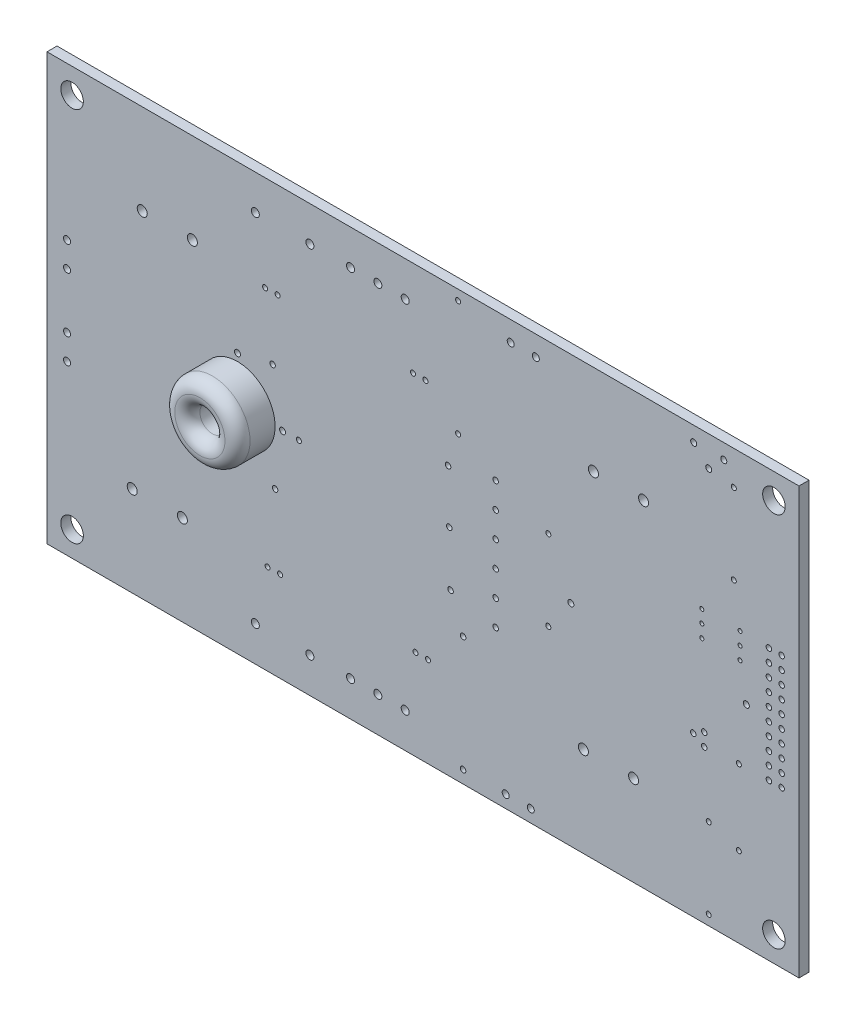
SolidWorks part; units mm, degrees
ref_plane "Спереди" through (0, 0, 0) normal (0, 0, 1) x (1, 0, 0)
ref_plane "Сверху" through (0, 0, 0) normal (0, 1, 0) x (1, 0, 0)
ref_plane "Справа" through (0, 0, 0) normal (1, 0, 0) x (0, 0, -1)
sketch "Эскиз1" plane through (0, 0, 0) normal (0, 0, 1) x (1, 0, 0)
  line L0 (-22.6071, 0) -> (23.7373, 0) construction
  line L1 (-75, -42.5) -> (75, -42.5)
  line L2 (-75, -42.5) -> (-75, 42.5)
  line L3 (-75, 42.5) -> (75, 42.5)
  line L4 (75, -42.5) -> (75, 42.5)
  line L5 (0, 0) -> (0, 31.6453) construction
  circle A0 centre (-70, -37.5) radius 2.25
  circle A1 centre (70, -37.5) radius 2.25
  circle A2 centre (70, 37.5) radius 2.25
  circle A3 centre (-70, 37.5) radius 2.25
  dimension "D3" = 4.5
  dimension "D1" = 150
  dimension "D2" = 85
  dimension "D4" = 5
  dimension "D5" = 5
extrude "Вытянуть1" add sketch "Эскиз1" along normal blind 2
sketch "Эскиз2" plane through (0, 0, 2) normal (0, 0, 1) x (1, 0, 0)
  line L0 (-75, 42.5) -> (-75, -42.5) construction
  line L1 (-75, -42.5) -> (75, -42.5) construction
  line L2 (-33.45, 35.5) -> (-22.55, 35.5) construction
  line L3 (-14.45, -35.5) -> (-3.55, -35.5) construction
  line L4 (69, 11.5) -> (71.54, 11.5) construction
  line L5 (14.5, -12.2) -> (47.2663, -12.2) construction
  line L6 (14.5, -12.2) -> (26.9466, 0.2466) construction
  line L7 (-24.75, 0.5) -> (5.25, 0.5) construction
  line L14 (63, -26.5) -> (63, -11.5) construction
  line L15 (-14.45, 35.5) -> (-3.55, 35.5) construction
  line L16 (-33.45, -35.5) -> (-22.55, -35.5) construction
  line L18 (14.5, -22.58) -> (14.5, -12.2) construction
  circle A0 centre (69, 11.5) radius 0.55
  circle A1 centre (71.54, 11.5) radius 0.55
  circle A2 centre (69, 8.96) radius 0.55
  circle A3 centre (71.54, 8.96) radius 0.55
  circle A4 centre (69, 6.42) radius 0.55
  circle A5 centre (71.54, 6.42) radius 0.55
  circle A6 centre (69, 3.88) radius 0.55
  circle A7 centre (71.54, 3.88) radius 0.55
  circle A8 centre (69, 1.34) radius 0.55
  circle A9 centre (71.54, 1.34) radius 0.55
  circle A10 centre (69, -1.2) radius 0.55
  circle A11 centre (71.54, -1.2) radius 0.55
  circle A12 centre (69, -3.74) radius 0.55
  circle A13 centre (71.54, -3.74) radius 0.55
  circle A14 centre (69, -6.28) radius 0.55
  circle A15 centre (71.54, -6.28) radius 0.55
  circle A16 centre (69, -8.82) radius 0.55
  circle A17 centre (71.54, -8.82) radius 0.55
  circle A18 centre (69, -11.36) radius 0.55
  circle A19 centre (71.54, -11.36) radius 0.55
  circle A20 centre (63, -26.5) radius 0.5
  circle A21 centre (63, -11.5) radius 0.5
  circle A22 centre (-14.45, 35.5) radius 0.8
  circle A23 centre (-9, 35.5) radius 0.8
  circle A24 centre (-3.55, 35.5) radius 0.8
  circle A25 centre (-33.45, 35.5) radius 0.8
  circle A26 centre (-24.75, 0.5) radius 0.5
  circle A27 centre (-22.55, 35.5) radius 0.8
  circle A28 centre (-33.45, -35.5) radius 0.8
  circle A29 centre (5.25, 0.5) radius 0.55
  circle A30 centre (-22.55, -35.5) radius 0.8
  circle A31 centre (-14.45, -35.5) radius 0.8
  circle A32 centre (-9, -35.5) radius 0.8
  circle A33 centre (-3.55, -35.5) radius 0.8
  circle A37 centre (14.5, 13.2) radius 0.55
  circle A38 centre (14.5, 8.12) radius 0.55
  circle A39 centre (14.5, -2.04) radius 0.55
  circle A40 centre (14.5, 3.04) radius 0.55
  circle A41 centre (14.5, -7.12) radius 0.55
  circle A45 centre (14.5, -12.2) radius 0.55
  dimension "D3" = 1.1
  dimension "D4" = 2.54
  dimension "D7" = 1
  dimension "D8" = 138
  dimension "D9" = 60.55
  dimension "D10" = 10.9
  dimension "D11" = 1.1
  dimension "D12" = 78
  dimension "D13" = 1.6
  dimension "D19" = 1.6
  dimension "D20" = 5.45
  dimension "D23" = 30
  dimension "D14" = 10.9
  dimension "D26" = 10.9
  dimension "D27" = 1.1
  dimension "D28" = 43
  dimension "D29" = 50.25
  dimension "D30" = 5.08
  dimension "D32" = 30.3
  dimension "D6" = 15
  dimension "D33" = 5.08
  dimension "D34" = 5.08
  dimension "D36" = 5.08
  dimension "D42" = 1.6
  dimension "D24" = 54
  dimension "D35" = 5.08
  dimension "D1" = 144
  dimension "D5" = 16
  dimension "D15" = 41.55
  dimension "D16" = 78
  dimension "D17" = 7
  dimension "D18" = 7
  dimension "D21" = 41.55
  dimension "D22" = 60.55
  dimension "D25" = 45
  dimension "D31" = 89.5
extrude "Вырез-Вытянуть1" cut sketch "Эскиз2" against normal blind 2
sketch "Эскиз3" plane through (0, 0, 2) normal (0, 0, 1) x (1, 0, 0)
  line L0 (-75, -42.5) -> (75, -42.5) construction
  line L1 (-75, 42.5) -> (-75, -42.5) construction
  line L2 (-56, 24.5) -> (-46, 24.5) construction
  line L3 (56.095, -10.75) -> (51.9719, -10.75) construction
  line L4 (56.095, -9.48) -> (56.095, -32.4484) construction
  line L5 (55, -12.02) -> (55, -7.4533) construction
  line L6 (16.5, -40) -> (21.5, -40) construction
  line L7 (-71, 7) -> (-71, 12) construction
  line L8 (-71, -9) -> (-71, -4) construction
  line L9 (-75, -42.5) -> (75, -42.5) construction
  line L11 (25, -6.75) -> (25, 9.25) construction
  line L12 (57, -40.5) -> (57, -24.5) construction
  line L14 (47.25, 45) -> (47.25, 55) construction
  line L16 (34, 24.5) -> (44, 24.5) construction
  line L17 (32, -24.5) -> (42, -24.5) construction
  line L18 (-58, -24.5) -> (-48, -24.5) construction
  line L19 (62, 19.75) -> (62, 35.75) construction
  line L20 (63.24, 11.58) -> (63.24, 6.5) construction
  line L21 (55.62, 6.5) -> (55.62, 12.7862) construction
  line L22 (55.62, 6.5) -> (63.24, 6.5) construction
  line L23 (54, 39.5) -> (60, 39.5) construction
  line L24 (17.5, 38.5) -> (22.5, 38.5) construction
  line L25 (29.5, -0.5) -> (64.5, -0.5) construction
  circle A0 centre (-56, 24.5) radius 1
  circle A1 centre (-46, 24.5) radius 1
  circle A2 centre (-58, -24.5) radius 1
  circle A3 centre (-48, -24.5) radius 1
  circle A4 centre (54, 39.5) radius 0.6
  circle A5 centre (60, 39.5) radius 0.6
  circle A6 centre (56.095, -9.48) radius 0.55
  circle A7 centre (56.095, -12.02) radius 0.55
  circle A8 centre (53.905, -10.75) radius 0.55
  circle A9 centre (70, -37.5) radius 2.25 construction
  circle A10 centre (16.5, -40) radius 0.7
  circle A12 centre (21.5, -40) radius 0.7
  circle A13 centre (-71, 7) radius 0.7
  circle A14 centre (-71, 12) radius 0.7
  circle A15 centre (-71, -9) radius 0.7
  circle A16 centre (-71, -4) radius 0.7
  circle A17 centre (25, -6.75) radius 0.5
  circle A18 centre (25, 9.25) radius 0.5
  circle A20 centre (57, -40.5) radius 0.5
  circle A21 centre (57, -24.5) radius 0.5
  circle A28 centre (34, 24.5) radius 1
  circle A29 centre (44, 24.5) radius 1
  circle A30 centre (32, -24.5) radius 1
  circle A31 centre (42, -24.5) radius 1
  circle A34 centre (57, 36.5) radius 0.6
  circle A35 centre (17.5, 38.5) radius 0.7
  circle A36 centre (62, 19.75) radius 0.5
  circle A37 centre (62, 35.75) radius 0.5
  circle A38 centre (63.24, 11.58) radius 0.4
  circle A39 centre (63.24, 6.5) radius 0.4
  circle A40 centre (55.62, 9.04) radius 0.4
  circle A41 centre (63.24, 9.04) radius 0.4
  circle A42 centre (55.62, 6.5) radius 0.4
  circle A43 centre (55.62, 11.58) radius 0.4
  circle A44 centre (22.5, 38.5) radius 0.7
  circle A45 centre (64.5, -0.5) radius 0.6
  circle A46 centre (29.5, -0.5) radius 0.6
  dimension "D5" = 1.1
  dimension "D8" = 2.54
  dimension "D9" = 2.19
  dimension "D10" = 1.095
  dimension "D11" = 15
  dimension "D16" = 91.5
  dimension "D17" = 5
  dimension "D18" = 49.5
  dimension "D22" = 1.2
  dimension "D23" = 1.2
  dimension "D24" = 16
  dimension "D25" = 35.75
  dimension "D28" = 1
  dimension "D44" = 10
  dimension "D14" = 5
  dimension "D15" = 2.5
  dimension "D30" = 16
  dimension "D35" = 10
  dimension "D20" = 1.4
  dimension "D50" = 1.4
  dimension "D56" = 19
  dimension "D58" = 18
  dimension "D59" = 16
  dimension "D63" = 7.62
  dimension "D64" = 2.54
  dimension "D65" = 5.08
  dimension "D67" = 130.62
  dimension "D70" = 6
  dimension "D72" = 6
  dimension "D76" = 5
  dimension "D77" = 1.4
  dimension "D78" = 35
  dimension "D12" = 26.75
  dimension "D19" = 4
  dimension "D21" = 5
  dimension "D29" = 2
  dimension "D31" = 132
  dimension "D34" = 10
  dimension "D38" = 122.25
  dimension "D45" = 67
  dimension "D46" = 109
  dimension "D47" = 10
  dimension "D48" = 18
  dimension "D49" = 107
  dimension "D51" = 4
  dimension "D52" = 33.5
  dimension "D57" = 67
  dimension "D60" = 137
  dimension "D61" = 62.25
  dimension "D62" = 5.08
  dimension "D66" = 49
  dimension "D68" = 17
  dimension "D69" = 3
  dimension "D71" = 82
  dimension "D73" = 129
  dimension "D74" = 81
  dimension "D75" = 92.5
  dimension "D79" = 42
  dimension "D80" = 104.5
extrude "Вырез-Вытянуть2" cut sketch "Эскиз3" against normal blind 10
sketch "Эскиз4" plane through (0, 0, 2) normal (0, 0, 1) x (1, 0, 0)
  line L0 (-37, -8.5) -> (-37, 9.45) construction
  line L1 (-75, 42.5) -> (-75, -42.5) construction
  line L2 (-75, -42.5) -> (75, -42.5) construction
  line L4 (-31.5, 23.5) -> (0.5, 23.5) construction
  line L5 (-11, 51) -> (-11, 74) construction
  line L6 (8, -40) -> (8, -17) construction
  line L7 (-75, 42.5) -> (-75, -42.5) construction
  line L8 (-68, 23) -> (-68, 56) construction
  line L9 (7, 17.5) -> (7, 40.5) construction
  line L10 (-39.9282, 0.5) -> (-22.3607, 0.5) construction
  line L11 (-30, 11) -> (5, 11) construction
  line L15 (-29.5, -10.25) -> (5.5, -10.25) construction
  line L16 (-31, -24.5) -> (1, -24.5) construction
  circle A0 centre (-37, -8.5) radius 0.6
  circle A1 centre (-28, 0.5) radius 0.6
  circle A2 centre (-31.5, 23.5) radius 0.5
  circle A3 centre (-37, 9.45) radius 0.6
  circle A6 centre (0.5, 23.5) radius 0.5
  circle A7 centre (-29, 23.5) radius 0.5
  circle A8 centre (-11, 51) radius 0.5
  circle A9 centre (-11, 74) radius 0.5
  circle A10 centre (-2, 23.5) radius 0.5
  circle A11 centre (8, -40) radius 0.55
  circle A12 centre (8, -17) radius 0.55
  circle A13 centre (-68, 56) radius 0.5
  circle A14 centre (-68, 51) radius 0.5
  circle A15 centre (7, 17.5) radius 0.5
  circle A16 centre (7, 40.5) radius 0.5
  circle A17 centre (-52, 56) radius 0.5
  circle A18 centre (-52, 51) radius 0.5
  circle A19 centre (-30, 11) radius 0.55
  circle A20 centre (5, 11) radius 0.55
  circle A21 centre (-35.5, 0.5) radius 0.6
  circle A40 centre (-29.5, -10.25) radius 0.55
  circle A41 centre (5.5, -10.25) radius 0.55
  circle A42 centre (-31, -24.5) radius 0.5
  circle A43 centre (1, -24.5) radius 0.5
  circle A44 centre (-28.5, -24.5) radius 0.5
  circle A45 centre (-1.5, -24.5) radius 0.5
  dimension "D5" = 2.5
  dimension "D10" = 32
  dimension "D12" = 66
  dimension "D15" = 64
  dimension "D19" = 83
  dimension "D24" = 5
  dimension "D25" = 35
  dimension "D26" = 7
  dimension "D29" = 1
  dimension "D31" = 5
  dimension "D37" = 17.95
  dimension "D38" = 43
  dimension "D39" = 45
  dimension "D40" = 53.5
  dimension "D71" = 27
  dimension "D72" = 32
  dimension "D73" = 2.5
  dimension "D74" = 44
  dimension "D13" = 23
  dimension "D18" = 2.5
  dimension "D22" = 82
  dimension "D23" = 60
  dimension "D27" = 32.25
  dimension "D28" = 45.5
  dimension "D30" = 1.1
  dimension "D14" = 23
  dimension "D16" = 93.5
  dimension "D17" = 9
  dimension "D34" = 3
  dimension "D35" = 9
  dimension "D36" = 1.2
  dimension "D21" = 23
  dimension "D33" = 1.1
  dimension "D3" = 38
  dimension "D4" = 27
  dimension "D11" = 43.5
  dimension "D32" = 35
  dimension "D67" = 18
extrude "Вырез-Вытянуть3" cut sketch "Эскиз4" against normal blind 10
sketch "Эскиз5" plane through (0, 0, 2) normal (0, 0, 1) x (1, 0, 0)
  line L0 (-37, -7.9) -> (-37, 10.05) construction
  line L1 (-43.7406, 0.5) -> (-24.6825, 0.5) construction
  line L3 (-75, 42.5) -> (-75, -42.5) construction
  line L6 (-75, -42.5) -> (75, -42.5) construction
  circle A0 centre (-37, 0.5) radius 2.5
  circle A1 centre (-37, 0.5) radius 7.5
  circle A4 centre (-37, -8.5) radius 0.6 construction
  circle A5 centre (-37, 9.45) radius 0.6 construction
  dimension "D1" = 5
  dimension "D2" = 15
  dimension "D3" = 38
  dimension "D4" = 43
extrude "Вытянуть2" add sketch "Эскиз5" along normal blind 7.5
fillet "Скругление1" radius 2.5 2 edges at (-34.5, 0.5, 9.5) (-29.5, 0.5, 9.5)
